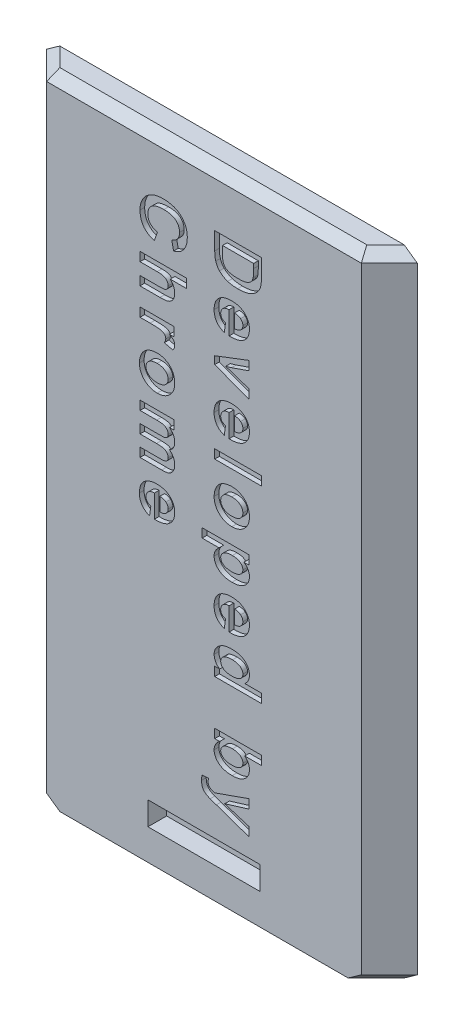
SolidWorks part; units mm, degrees
material "Custom Plastic"
ref_plane "Front Plane" through (0, 0, 0) normal (0, 0, 1) x (1, 0, 0)
ref_plane "Top Plane" through (0, 0, 0) normal (0, 1, 0) x (1, 0, 0)
ref_plane "Right Plane" through (0, 0, 0) normal (1, 0, 0) x (0, 0, -1)
sketch "Sketch1" plane through (0, 0, 0) normal (0, 0, 1) x (1, 0, 0)
  line L1 (0, 0) -> (39.7, 0)
  line L2 (0, 0) -> (0, 68)
  line L3 (0, 68) -> (39.7, 68)
  line L4 (39.7, 0) -> (39.7, 68)
  dimension "D1" = 39.7
  dimension "D2" = 68
extrude "Boss-Extrude1" add sketch "Sketch1" along normal blind 3
sketch "Sketch2" plane through (0, 0, 0) normal (0, -1, 0) x (1, 0, 0)
  line L0 (0, 0) -> (0, 3)
  line L1 (0, 3) -> (3, 3)
  line L2 (0, 3) -> (39.7, 3) construction
  line L3 (3, 3) -> (0, 0)
  line L4 (39.7, 0) -> (39.7, 3)
  line L5 (39.7, 3) -> (36.7, 3)
  line L6 (36.7, 3) -> (39.7, 0)
  dimension "D1" = 135
  dimension "D2" = 135
extrude "Cut-Extrude2" cut sketch "Sketch2" against normal blind 68
sketch "Sketch3" plane through (0, 0, 3) normal (0, 0, 1) x (1, 0, 0)
  line L0 (21, 62.6863) -> (21, 4.7448) construction
  line L1 (13, 62.6863) -> (13, 4.7448) construction
  line L2 (3, 68) -> (3, 0) construction
  text T0 "Developed by" font "Arial" height 5
  text T1 "Chrome" font "Arial" height 5
  point P5 (21, 62.6863)
  point P8 (13, 62.6863)
  point P9 (21, 4.7448)
  point P10 (13, 4.7448)
  dimension "D1" = 10
  dimension "D2" = 18
extrude "Cut-Extrude3" cut sketch "Sketch3" against normal blind 0.5
sketch "Sketch4" plane through (0, 0, 3) normal (0, 0, 1) x (1, 0, 0)
  line L0 (3, 68) -> (3, 0) construction
  line L1 (13.85, 5.8071) -> (25.85, 5.8071)
  line L2 (13.85, 5.8071) -> (13.85, 3.3071)
  line L3 (13.85, 3.3071) -> (25.85, 3.3071)
  line L4 (25.85, 5.8071) -> (25.85, 3.3071)
  dimension "D1" = 2.5
  dimension "D2" = 12
  dimension "D3" = 10.85
extrude "Cut-Extrude4" cut sketch "Sketch4" against normal blind 2
chamfer "Chamfer1" distance 1 angle 45 3 edges at (38.2, 68, 1.5) (1.5, 68, 1.5) (19.85, 68, 3)
chamfer "Chamfer2" distance 1 angle 45 2 edges at (38.2, 0, 1.5) (1.5, 0, 1.5)
